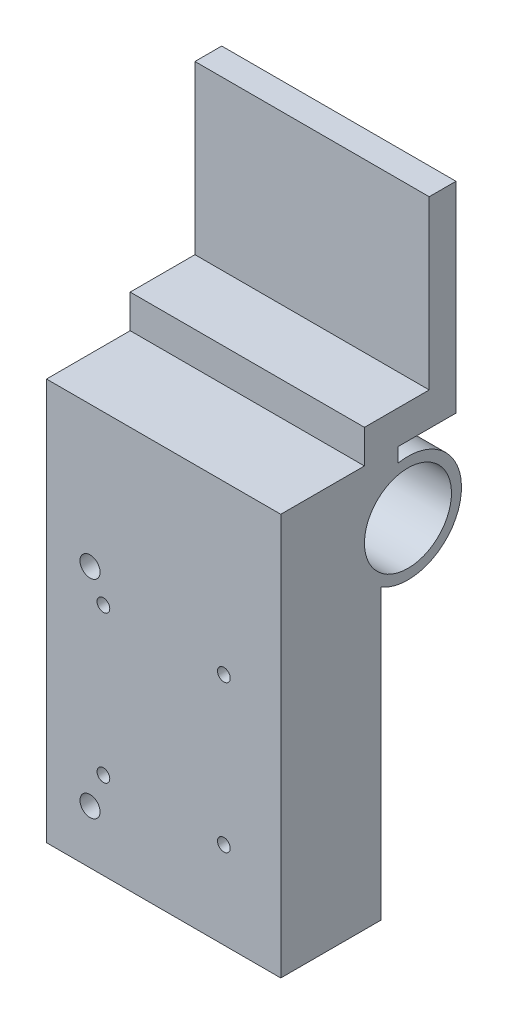
SolidWorks part; units mm, degrees
ref_plane "Front Plane" through (0, 0, 0) normal (0, 0, 1) x (1, 0, 0)
ref_plane "Top Plane" through (0, 0, 0) normal (0, 1, 0) x (1, 0, 0)
ref_plane "Right Plane" through (0, 0, 0) normal (1, 0, 0) x (0, 0, -1)
sketch "Sketch1" plane through (0, 0, 0) normal (0, 0, 1) x (1, 0, 0)
  line L1 (0, 0) -> (-35, 0)
  line L2 (0, 0) -> (0, 60)
  line L3 (0, 60) -> (-35, 60)
  line L4 (-35, 0) -> (-35, 60)
  dimension "D1" = 60
  dimension "D2" = 35
extrude "Boss-Extrude1" add sketch "Sketch1" along normal blind 15
sketch "Sketch2" plane through (0, 0, 15) normal (0, 0, 1) x (1, 0, 0)
  line L0 (-35, 60) -> (-35, 0) construction
  line L1 (-35, 0) -> (0, 0) construction
  circle A0 centre (-28.5, 8) radius 1.5
  circle A1 centre (-26.5, 13) radius 0.95
  circle A2 centre (-26.5, 35) radius 0.95
  circle A3 centre (-28.5, 39) radius 1.5
  dimension "D1" = 3
  dimension "D4" = 1.9
  dimension "D8" = 39
  dimension "D2" = 6.5
  dimension "D3" = 8
  dimension "D5" = 13
  dimension "D6" = 2
  dimension "D7" = 22
extrude "Cut-Extrude1" cut sketch "Sketch2" against normal through all
ref_plane "Plane1" through (-17.5, 0, 0) normal (1, 0, 0) x (0, 0, -1)
mirror "Mirror1" about plane through (-17.5, 0, 0) normal (1, 0, 0) of face at (-25.55, 13, 0) of face at (-25.55, 35, 0)
sketch "Sketch3" plane through (-35, 0, 0) normal (-1, 0, 0) x (0, 0, 1)
  circle A0 centre (-4, 50) radius 8
  dimension "D1" = 16
  dimension "D2" = 50
  dimension "D3" = 4
extrude "Boss-Extrude2" add sketch "Sketch3" against normal blind 12
sketch "Sketch4" plane through (-35, 0, 0) normal (-1, 0, 0) x (0, 0, 1)
  circle A0 centre (-4, 50) radius 6.5
  arc A1 (0, 56.9282) -> (0, 43.0718) centre (-4, 50) ccw construction
  dimension "D1" = 13
extrude "Cut-Extrude2" cut sketch "Sketch4" against normal through all
mirror "Mirror2" about plane through (-17.5, 0, 0) normal (1, 0, 0) of "Boss-Extrude2", "Cut-Extrude2"
sketch "Sketch5" plane through (0, 60, 0) normal (0, 1, 0) x (1, 0, 0)
  line L0 (-35, -15) -> (-35, 0) construction
  line L1 (-35, -2.5) -> (0, -2.5)
  line L2 (-35, -2.5) -> (-35, 2.5)
  line L3 (-35, 2.5) -> (0, 2.5)
  line L4 (0, -2.5) -> (0, 2.5)
  line L5 (0, 0) -> (0, 12) construction
  point P8 (-35, 0)
  dimension "D1" = 5
extrude "Boss-Extrude4" add sketch "Sketch5" along normal blind 5 and the other way up to surface other way up to face at (-29, 50, -6)
sketch "Sketch12" plane through (-35, 0, 0) normal (-1, 0, 0) x (0, 0, 1)
  line L0 (-2.5, 65) -> (-7.175, 65)
  line L1 (-7.175, 65) -> (-7.175, 90)
  line L2 (-7.175, 90) -> (-11.175, 90)
  line L3 (-11.175, 90) -> (-11.175, 60)
  line L4 (-11.175, 60) -> (-2.5, 60)
  line L5 (-2.5, 57.8581) -> (-2.5, 65) construction
  line L6 (-2.5, 60) -> (-2.5, 65)
  circle A0 centre (-4, 50) radius 6.5 construction
  dimension "D1" = 3.175
  dimension "D2" = 25
  dimension "D3" = 4
  dimension "D4" = 5
extrude "Boss-Extrude7" add sketch "Sketch12" against normal through all
